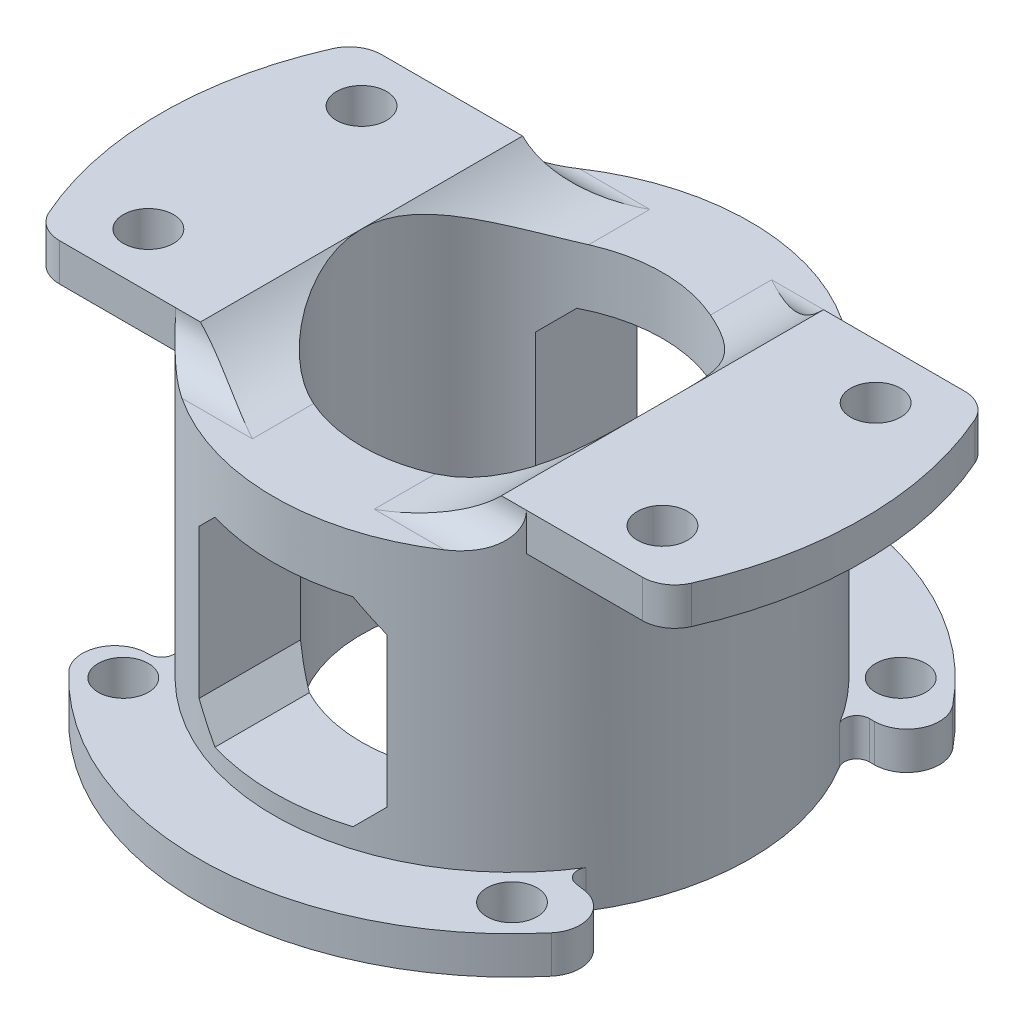
SolidWorks part; units mm, degrees
ref_plane "前视基准面" through (0, 0, 0) normal (0, 0, 1) x (1, 0, 0)
ref_plane "上视基准面" through (0, 0, 0) normal (0, 1, 0) x (1, 0, 0)
ref_plane "右视基准面" through (0, 0, 0) normal (1, 0, 0) x (0, 0, -1)
sketch "草图1" plane through (0, 0, 0) normal (0, 1, 0) x (1, 0, 0)
  circle A0 centre (0, 0) radius 25
  dimension "D1" = 50
extrude "凸台-拉伸1" add sketch "草图1" along normal blind 3 contours A0
sketch "草图2" plane through (0, 0, 0) normal (0, 1, 0) x (1, 0, 0)
  line L1 (-15.5, 15.5) -> (15.5, 15.5)
  line L2 (-15.5, 15.5) -> (-15.5, -15.5)
  line L3 (-15.5, -15.5) -> (15.5, -15.5)
  line L4 (15.5, 15.5) -> (15.5, -15.5)
  line L5 (0, -15.5) -> (0, 15.5) construction
  line L6 (-15.5, 0) -> (15.5, 0) construction
  point P0 (0, 0)
  dimension "D1" = 31
  dimension "D2" = 31
sketch "草图13" plane through (0, 3, 0) normal (0, 1, 0) x (1, 0, 0)
  circle A0 centre (0, 0) radius 19
  dimension "D1" = 38
extrude "凸台-拉伸3" add sketch "草图13" along normal blind 22
sketch "草图6" plane through (0, 25, 0) normal (0, 1, 0) x (1, 0, 0)
  circle A0 centre (0, 0) radius 28
  dimension "D1" = 56
extrude "凸台-拉伸2" add sketch "草图6" along normal blind 3 contours A0
sketch "草图5" plane through (0, 28, 0) normal (0, 1, 0) x (1, 0, 0)
  line L0 (-15.5, 0) -> (15.5, 0) construction
  circle A0 centre (0, 0) radius 12
  dimension "D1" = 24
hole_wizard "大小mm 暗销孔2" positions "草图7" profile "草图8" hole size "Ø4.0" standard "GB"
sketch "草图7" plane through (0, 0, 0) normal (0, -1, 0) x (-1, 0, 0)
  point P0 (-15.5, 15.5)
  point P3 (15.5, 15.5)
  point P6 (15.5, -15.5)
  point P9 (-15.5, -15.5)
sketch "草图8" plane through (15.5, 0, -15.5) normal (1, 0, 0) x (0, 0, -1)
  line L0 (0, 0) -> (0, 3)
  line L1 (0, 3) -> (2, 3)
  line L2 (2, 3) -> (2, 0)
  line L5 (2, 0) -> (0, 0)
  line L11 (0, -6.35) -> (0, 107.95) construction
  dimension "通孔孔直径" = 4
  dimension "通孔孔深度" = 3
extrude "切除-拉伸2" cut sketch "草图5" against normal through all
sketch "草图9" plane through (0, 28, 0) normal (0, 1, 0) x (1, 0, 0)
  line L0 (-28, 0) -> (28, 0) construction
  line L3 (0, -28) -> (0, 28) construction
  circle A0 centre (0, 0) radius 28 construction
  point P0 (-22, 0)
  point P3 (0, 0)
  point P4 (22, 0)
  point P10 (0, 0)
  dimension "D1" = 44
sketch "草图17" plane through (0, 28, 0) normal (0, 1, 0) x (1, 0, 0)
  circle A0 centre (-20.5, -8.5) radius 2
  circle A1 centre (-20.5, 8.5) radius 2
  circle A2 centre (20.5, 8.5) radius 2
  circle A3 centre (20.5, -8.5) radius 2
  dimension "D1" = 4
  dimension "D2" = 4
  dimension "D3" = 4
  dimension "D4" = 4
extrude "切除-拉伸7" cut sketch "草图17" against normal up to next
sketch "草图12" plane through (0, 0, 0) normal (0, -1, 0) x (1, 0, 0)
  line L2 (-21, 21) -> (21, 21)
  line L3 (-21, 21) -> (-21, -21)
  line L4 (-21, -21) -> (21, -21)
  line L5 (21, 21) -> (21, -21)
  line L6 (0, -21) -> (0, 21) construction
  line L7 (-21, 0) -> (21, 0) construction
  point P2 (0, 0)
  dimension "D1" = 42
  dimension "D2" = 42
sketch "草图14" plane through (0, 28, 0) normal (0, 1, 0) x (1, 0, 0)
  line L0 (0, 0) -> (20.7735, 0) construction
  line L1 (-30.3012, -12.8468) -> (34.2841, -12.8468)
  line L2 (-30.3012, -12.8468) -> (-30.3012, -31.0868)
  line L3 (-30.3012, -31.0868) -> (34.2841, -31.0868)
  line L4 (34.2841, -12.8468) -> (34.2841, -31.0868)
  line L5 (-26.084, 30.1059) -> (35.6117, 30.1059)
  line L6 (-26.084, 30.1059) -> (-26.084, 12.8468)
  line L7 (-26.084, 12.8468) -> (35.6117, 12.8468)
  line L8 (35.6117, 30.1059) -> (35.6117, 12.8468)
extrude "切除-拉伸4" cut sketch "草图14" against normal up to surface (3 mm away) up to face at (20.5, 25, 10.5)
sketch "草图15" plane through (0, 0, 0) normal (0, -1, 0) x (1, 0, 0)
  line L0 (-24.8789, 12.8468) -> (-13.9986, 12.8468)
  line L1 (0, 0) -> (0, 9.2092)
  line L2 (24.8789, 12.8468) -> (15.1691, 11.441)
  line L3 (0, 0) -> (4.0327, 0)
  line L4 (25.5559, -11.441) -> (15.1691, -11.441)
  line L5 (-25.5559, -11.441) -> (-15.1691, -11.441)
  arc A2 (-24.8789, 12.8468) -> (-25.5559, -11.441) centre (0, 0) ccw
  arc A3 (15.1691, -11.441) -> (15.1691, 11.441) centre (0, 0) ccw
  arc A4 (24.8789, 12.8468) -> (25.5559, -11.441) centre (0, 0) cw
  arc A6 (-13.9986, 12.8468) -> (-15.1691, -11.441) centre (0, 0) ccw
  circle M4 centre (0, 0) radius 12
  circle M8 centre (0, 0) radius 25
extrude "切除-拉伸5" cut sketch "草图15" against normal up to surface (3 mm away) contours L5 L0 M8 M4 | L4 L2 M8 M4 up to face at (15.5, 3, -13.5)
fillet "圆角1" radius 2.6 8 edges at (-21.4467, 1.5, 12.8468) (-22.2284, 1.5, -11.441) (22.2284, 1.5, -11.441) (21.7145, 1.5, 12.3886) (-24.8789, 26.5, 12.8468) (24.8789, 26.5, 12.8468) (24.8789, 26.5, -12.8468) (-24.8789, 26.5, -12.8468)
fillet "圆角2" radius 1 4 edges at (-15.1691, 1.5, -11.441) (-13.9986, 1.5, 12.8468) (15.1691, 1.5, -11.441) (15.1691, 1.5, 11.441)
sketch "草图16" plane through (0, 0, 0) normal (0, 0, 1) x (1, 0, 0)
  line L0 (23.2414, 28) -> (-23.2414, 28) construction
  line L1 (-7.5, 20.4443) -> (7.5, 20.4443)
  line L2 (-7.5, 20.4443) -> (-7.5, 4.5557)
  line L3 (-7.5, 4.5557) -> (7.5, 4.5557)
  line L4 (7.5, 20.4443) -> (7.5, 4.5557)
  line L5 (0, 4.5557) -> (0, 20.4443) construction
  line L6 (-7.5, 12.5) -> (7.5, 12.5) construction
  line L7 (-12, 28) -> (12, 28)
  line L8 (-12, 28) -> (-12, 25)
  line L9 (-12, 25) -> (12, 25)
  line L10 (12, 28) -> (12, 25)
  line L12 (0, 25) -> (0, 28) construction
  point P0 (0, 12.5)
  point P12 (0, 0)
  dimension "D1" = 15
  dimension "D2" = 24
extrude "切除-拉伸6" cut sketch "草图16" against normal through all both and the other way through all
fillet "圆角3" radius 10 4 edges at (-12, 25, -6.4234) (12, 25, -6.4234) (-12, 25, 6.4234) (12, 25, 6.4234)
fillet "圆角4" radius 3 4 edges at (-9.4286, 25, -12.8468) (9.4286, 25, -12.8468) (9.4286, 25, 12.8468) (-9.4286, 25, 12.8468)
chamfer "倒角1" distance 2 angle 45 8 edges at (7.5, 20.4443, -13.4123) (7.5, 20.4443, 13.4123) (-7.5, 20.4443, -13.4123) (-7.5, 20.4443, 13.4123) (-7.5, 4.5557, 13.4123) (-7.5, 4.5557, -13.4123) (7.5, 4.5557, 13.4123) (7.5, 4.5557, -13.4123)
